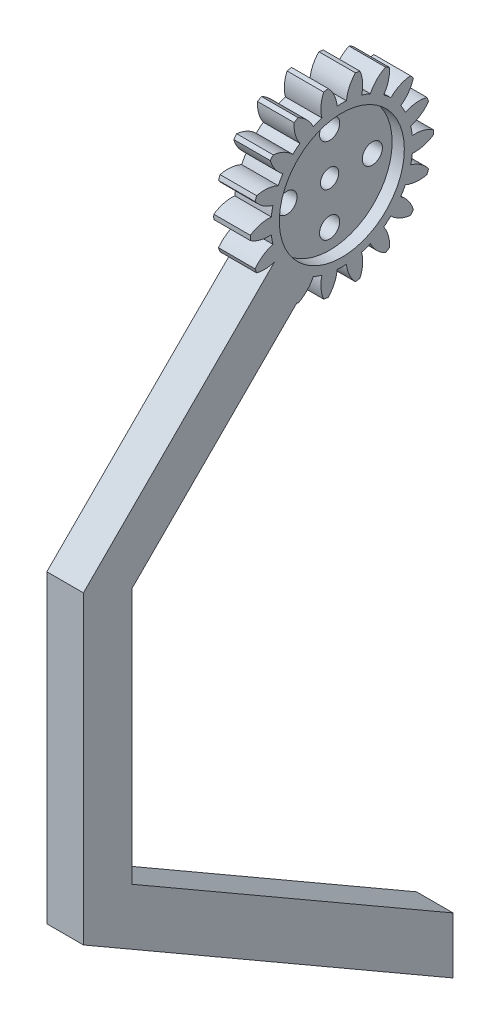
SolidWorks part; units mm, degrees
ref_plane "Plane1" through (0, 0, 0) normal (0, 0, 1) x (1, 0, 0)
ref_plane "Plane2" through (0, 0, 0) normal (0, 1, 0) x (1, 0, 0)
ref_plane "Plane3" through (0, 0, 0) normal (1, 0, 0) x (0, 0, -1)
other "Configuration Table"
sketch "HoldingSke" plane through (0, 0, 0) normal (0, 1, 0) x (1, 0, 0)
  line L0 (0, 0) -> (0.634, -0.206)
  line L1 (-15, 0) -> (100, 0) construction
  line L2 (0, 0) -> (-2.1039, 2.3779)
  line L3 (0, 0) -> (-11.863, 4.5341)
  line L4 (0, 0) -> (8.2133, 2.6687)
  line L5 (0, 0) -> (-46.8476, -17.4728)
  line L6 (0, 0) -> (-4.9738, -3.3558)
  line L7 (-2.1039, 2.3779) -> (8.6586, 51.2059)
  line L8 (-76.2, 54.61) -> (-75.7, 54.61)
  line L9 (-71.009, 38.7566) -> (-53.1078, 45.2721)
  line L10 (-76.2, 71.12) -> (104.1128, 71.12)
  line L11 (0, 0) -> (-6, 0)
  line L12 (-76.2, 101.6) -> (-76.147, 101.6)
  line L13 (24.9733, 27.94) -> (52.9518, 28.4284)
  line L14 (24.9733, 27.94) -> (24.9743, 27.94)
  line L15 (24.9733, 27.94) -> (100.4006, 29.5858)
  line L16 (-63.627, -1.5) -> (-12.827, -1.5)
  circle A0 centre (0, 0) radius 1.5
  circle A1 centre (0, 0) radius 11.624
  circle A2 centre (0, 0) radius 37.5
  circle A3 centre (0, 0) radius 1.5
  dimension "Num_teeth" = 18
  dimension "Pitch_radius" = 180.3128
  dimension "Width" = 6
  dimension "Thickness" = 6
sketch "BasProSke" plane through (0, 0, 0) normal (0, 1, 0) x (1, 0, 0)
  line L0 (-10, 0) -> (60, 0) construction
  line L1 (0, 0) -> (0, 15)
  line L2 (0, 0) -> (6, 0)
  line L3 (6, 0) -> (6, 15)
  line L4 (6, 15) -> (0, 15)
  dimension "Thickness" = 6
  dimension "Diameter" = 30
revolve "Base-Revolve" add sketch "BasProSke" angle 360 about L0
sketch "TooCutSke" plane through (0, 0, 0) normal (1, 0, 0) x (0, 0, -1)
  line L1 (0, 0) -> (0, 107) construction
  line L2 (0, 0) -> (-1.2693, 13.4402) construction
  line L3 (0, 0) -> (-4.6734, 26.504) construction
  line L4 (-1.2693, 13.4402) -> (-2.3367, 13.252) construction
  arc A0 (0.76, 11.5991) -> (-0.76, 11.5991) centre (0, 0) ccw
  arc A1 (2.2542, 14.8553) -> (-2.2542, 14.8553) centre (0, 0) ccw
  circle A2 centre (0, 0) radius 13.5 construction
  circle A3 centre (0, 0) radius 12.6859 construction
  arc A4 (-0.76, 11.5991) -> (-2.2542, 14.8553) centre (-6.1371, 11.1026) ccw
  arc A5 (2.2542, 14.8553) -> (0.76, 11.5991) centre (6.1371, 11.1026) ccw
extrude "ToothCut" cut sketch "TooCutSke" along normal through all
fillet "Breaks" [suppressed] radius 0.03 tangent propagation no
fillet "RootFillets" [suppressed] radius 0.376
pattern_circular "TeethCuts" count 18 every 20 about axis through (-10, 0, 0) along (1, 0, 0) of "ToothCut", "RootFillets", "Breaks"
sketch "HubNeaOneSke" plane through (0, 0, 0) normal (-1, 0, 0) x (0, 0, 1)
  circle A0 centre (0, 0) radius 11.624
  dimension "Diameter" = 23.248
extrude "HubNearOne" [suppressed] add sketch "HubNeaOneSke" along normal blind 44.0001
sketch "HubNeaBotSke" plane through (0, 0, 0) normal (-1, 0, 0) x (0, 0, 1)
  circle A0 centre (0, 0) radius 11.624
  dimension "Diameter" = 23.248
extrude "HubNearBoth" [suppressed] add sketch "HubNeaBotSke" along normal blind 22
ref_plane "FarPln" through (6, 0, 0) normal (1, 0, 0) x (0, 0, -1)
sketch "HubFarSke" plane through (6, 0, 0) normal (1, 0, 0) x (0, 0, -1)
  circle A0 centre (0, 0) radius 11.624
  dimension "Diameter" = 23.248
extrude "HubFar" [suppressed] add sketch "HubFarSke" along normal blind 22
sketch "BorSke" plane through (0, 0, 0) normal (1, 0, 0) x (0, 0, -1)
  circle A0 centre (0, 0) radius 1.5
extrude "Bore" cut sketch "BorSke" along normal mid plane 100.0001
sketch "KeySke" plane through (0, 0, 0) normal (1, 0, 0) x (0, 0, -1)
  line L0 (-0.6, 0) -> (-0.6, 2)
  line L1 (-0.6, 2) -> (0.6, 2)
  line L2 (0.6, 2) -> (0.6, 0)
  line L3 (0, 0) -> (0, 34) construction
  line L4 (-0.6, 0) -> (0.6, 0)
  dimension "Width" = 1.2
extrude "Keyway" [suppressed] cut sketch "KeySke" along normal mid plane 100.0001
pattern_circular "Keyway2" [suppressed] count 2 every 90 about axis through (-10, 0, 0) along (1, 0, 0)
move or copy body "右爪齿相_绕轴转半齿10度" [suppressed] bodies to move or copy 103 copy no rotation origin (0, 0, 0) rotation axis (-1, 0, 0) rotation angle 10
sketch "草图1" plane through (6, 0, 0) normal (1, 0, 0) x (0, 0, -1)
  line L0 (0, 0) -> (-8.2194, -8.2194) construction
  line L1 (0, 0) -> (0, -11.624) construction
  line L2 (-10.5459, -4.889) -> (-42.3657, -36.7088)
  line L3 (-10.5459, -4.889) -> (-4.889, -10.5459)
  line L4 (-42.3657, -36.7088) -> (-36.7088, -42.3657) construction
  line L5 (-4.889, -10.5459) -> (-36.7088, -42.3657) construction
  line L6 (-10.5459, -4.889) -> (-36.7088, -42.3657) construction
  line L7 (-42.3657, -36.7088) -> (-4.889, -10.5459) construction
  line L8 (-42.3657, -36.7088) -> (-42.3657, -86.7088)
  line L9 (-42.3657, -86.7088) -> (18.2561, -121.7088)
  line L10 (18.2561, -121.7088) -> (18.2561, -112.4712)
  line L11 (18.2561, -112.4712) -> (-34.3657, -82.09)
  line L12 (-34.3657, -82.09) -> (-34.3657, -40.0225)
  line L13 (-4.889, -10.5459) -> (-34.3657, -40.0225)
  circle A0 centre (0, 0) radius 11.624 construction
  arc A1 (11.5549, 1.2657) -> (11.2909, 2.7626) centre (0, 0) ccw construction
  arc A2 (11.5549, 1.2657) -> (11.2909, 2.7626) centre (0, 0) ccw construction
  point P2 (-23.6273, -23.6273)
  point P17 (-34.3657, -40.0225)
  dimension "D1" = 45
  dimension "D2" = 8
  dimension "D3" = 8
  dimension "D4" = 8
  dimension "D5" = 45
  dimension "D6" = 50
  dimension "D7" = 70
  dimension "D8" = 135
  dimension "D9" = 120
extrude "凸台-拉伸2" add sketch "草图1" against normal blind 6
sketch "草图2" plane through (6, 0, 0) normal (1, 0, 0) x (0, 0, -1)
  circle A0 centre (0, 0) radius 7 construction
  circle A1 centre (-7, 0) radius 1.65
  circle A2 centre (0, 7) radius 1.65
  circle A3 centre (7, 0) radius 1.65
  circle A4 centre (0, -7) radius 1.65
  point P14 (0, 0)
  dimension "D1" = 3.3
  dimension "D2" = 14
  dimension "D3" = 4
extrude "切除-拉伸1" cut sketch "草图2" against normal blind 6
sketch "草图3" plane through (6, 0, 0) normal (1, 0, 0) x (0, 0, -1)
  circle A0 centre (0, 0) radius 10.25
  dimension "D1" = 20.5
extrude "切除-拉伸2" cut sketch "草图3" against normal blind 2
ref_axis "夹爪啮合转轴" through (4, 0, 0) along (-1, 0, 0)
equation "' \"Module@HoldingSke\" = 6.35"
equation "' \"Num_teeth@HoldingSke\" = 12"
equation "' \"Ap@HoldingSke\" =  20"
equation "' \"Ap@HoldingSke\" = 20"
equation "' \"Width@HoldingSke\" = 0.5 * 25.4"
equation "' \"Hub_dia@HoldingSke\"= 1 * 25.4"
equation "' \"Hub_dia@HoldingSke\" = 1 * 25.4"
equation "' \"Overall_len@HoldingSke\" = 1.0 * 25.4"
equation "' \"Bore@HoldingSke\" = 0.75 * 25.4"
equation "' \"T_dim@HoldingSke\" = 0.1 * 25.4"
equation "' \"Width@KeySke\" = 0.25 * 25.4"
equation "' \"Show_teeth@HoldingSke\" = 13"
equation "' \"Backlash@HoldingSke\" = 0.009 * 25.4"
equation "' \"Addendum_fac@HoldingSke\" = 1.0"
equation "' \"Dedendum_fac@HoldingSke\" = 1.25"
equation "' \"Dedendum_add@HoldingSke\" = 0.00005 * 25.4"
equation "' \"Clearance_fac@HoldingSke\" = 0.25"
equation "\"Pitch@HoldingSke\" = 1 / \"Module@HoldingSke\""
equation "\"Overcut_dia@TooCutSke\" = (\"Num_teeth@HoldingSke\" + 2 * \"Addendum_fac@HoldingSke\") / \"Pitch@HoldingSke\" + 0.002 * 25.4"
equation "\"Pitch_dia@TooCutSke\" = \"Num_teeth@HoldingSke\" / \"Pitch@HoldingSke\""
equation "\"Base_dia@TooCutSke\" = \"Num_teeth@HoldingSke\" / \"Pitch@HoldingSke\" * cos((\"Ap@HoldingSke\"  * 3.14159265 / 180))"
equation "\"Root_dia@TooCutSke\" = (\"Num_teeth@HoldingSke\" + 2) / \"Pitch@HoldingSke\" - 2 * (\"Addendum_fac@HoldingSke\" + \"Dedendum_fac@HoldingSke\") / \"Pitch@HoldingSke\" - \"Dedendum_add@HoldingSke\" * 2"
equation "\"Half_ang@TooCutSke\" = 180 / \"Num_teeth@HoldingSke\""
equation "\"Half_CT@TooCutSke\" = \"Num_teeth@HoldingSke\" / \"Pitch@HoldingSke\" * sin((3.14159265 / 2 / \"Num_teeth@HoldingSke\")) / 2 - 7 * \"Backlash@HoldingSke\" / 4"
equation "\"Flank_rad@TooCutSke\" = \"Num_teeth@HoldingSke\" / \"Pitch@HoldingSke\" / 5"
equation "\"Radius@RootFillets\" = \"Clearance_fac@HoldingSke\" / \"Pitch@HoldingSke\" + \"Dedendum_add@HoldingSke\""
equation "\"Break_rad@Breaks\" = 0.02 / \"Pitch@HoldingSke\""
equation "\"Thickness@HoldingSke\" = \"Width@HoldingSke\""
equation "\"OAL@HoldingSke\" = \"Thickness@HoldingSke\""
equation "\"MHD@HoldingSke\" = (\"Num_teeth@HoldingSke\" + 2) / \"Pitch@HoldingSke\" - 2 * (\"Addendum_fac@HoldingSke\" + \"Dedendum_fac@HoldingSke\")  / \"Pitch@HoldingSke\" - \"Dedendum_add@HoldingSke\" * 2"
equation "\"MBD@HoldingSke\" = (\"Num_teeth@HoldingSke\" + 2) / \"Pitch@HoldingSke\" - 2 * (\"Addendum_fac@HoldingSke\" + \"Dedendum_fac@HoldingSke\")  / \"Pitch@HoldingSke\" - \"Dedendum_add@HoldingSke\" * 2 - 0.002 * 25.4"
equation "\"MHD@HoldingSke\" = ((sgn( \"MHD@HoldingSke\" - \"Hub_dia@HoldingSke\" )-1)*( \"MHD@HoldingSke\" - \"Hub_dia@HoldingSke\" ))/-2+ \"Hub_dia@HoldingSke\""
equation "\"MBD@HoldingSke\" = ((sgn( \"MBD@HoldingSke\" - \"Bore@HoldingSke\" )-1)*( \"MBD@HoldingSke\" - \"Bore@HoldingSke\" ))/-2+ \"Bore@HoldingSke\""
equation "\"OAL@HoldingSke\" = ((sgn( \"OAL@HoldingSke\" - \"Overall_len@HoldingSke\" )+1)*( \"OAL@HoldingSke\" - \"Overall_len@HoldingSke\" ))/2 + \"Overall_len@HoldingSke\" + 0.000002 * 25.4"
equation "\"Num_teeth@TeethCuts\" = int( \"Show_teeth@HoldingSke\" ) + 1"
equation "\"Num_teeth@TeethCuts\" = ((sgn( \"Num_teeth@TeethCuts\" - \"Num_teeth@HoldingSke\" )-1)*( \"Num_teeth@TeethCuts\" - \"Num_teeth@HoldingSke\" ))/-2+ \"Num_teeth@HoldingSke\""
equation "\"Num_teeth@TeethCuts\" = ((sgn( \"Num_teeth@TeethCuts\" - 2.0)+1)*( \"Num_teeth@TeethCuts\" - 2.0))/2 +2.0"
equation "\"Angle@TeethCuts\" = 360.0 / \"Num_teeth@HoldingSke\""
equation "\"Diameter@BasProSke\" = (\"Num_teeth@HoldingSke\" + 2 * \"Addendum_fac@HoldingSke\") / \"Pitch@HoldingSke\""
equation "\"Thickness@BasProSke\"  = \"Thickness@HoldingSke\""
equation "' \"Fillet_rad@BasProSke\" =  \"Thickness@HoldingSke\" * 0.05"
equation "' \"Fillet_rad@BasProSke\" = \"Thickness@HoldingSke\" * 0.05"
equation "\"MHD@HoldingSke\" = ((sgn( \"MHD@HoldingSke\" - \"Root_dia@TooCutSke\" )-1)*( \"MHD@HoldingSke\" - \"Root_dia@TooCutSke\" ))/-2+ \"Root_dia@TooCutSke\""
equation "\"Diameter@HubNeaOneSke\" = \"MHD@HoldingSke\""
equation "\"Length@HubNearOne\" = \"OAL@HoldingSke\" - \"Thickness@BasProSke\""
equation "\"Diameter@HubNeaBotSke\" = \"MHD@HoldingSke\""
equation "\"Length@HubNearBoth\" = ( \"OAL@HoldingSke\" - \"Thickness@BasProSke\" ) / 2.0"
equation "\"Thickness@FarPln\" = \"Thickness@BasProSke\""
equation "\"Diameter@HubFarSke\" = \"MHD@HoldingSke\""
equation "\"Length@HubFar\" = ( \"OAL@HoldingSke\" - \"Thickness@BasProSke\" ) / 2.0"
equation "\"Diameter@BorSke\" = \"MBD@HoldingSke\""
equation "\"D1@Bore\" = \"OAL@HoldingSke\" * 2.0"
equation "\"D1@Keyway\" = \"OAL@HoldingSke\" * 2.0"
equation "\"Offset@KeySke\" = \"T_dim@HoldingSke\" + \"MBD@HoldingSke\" / 2.0"
